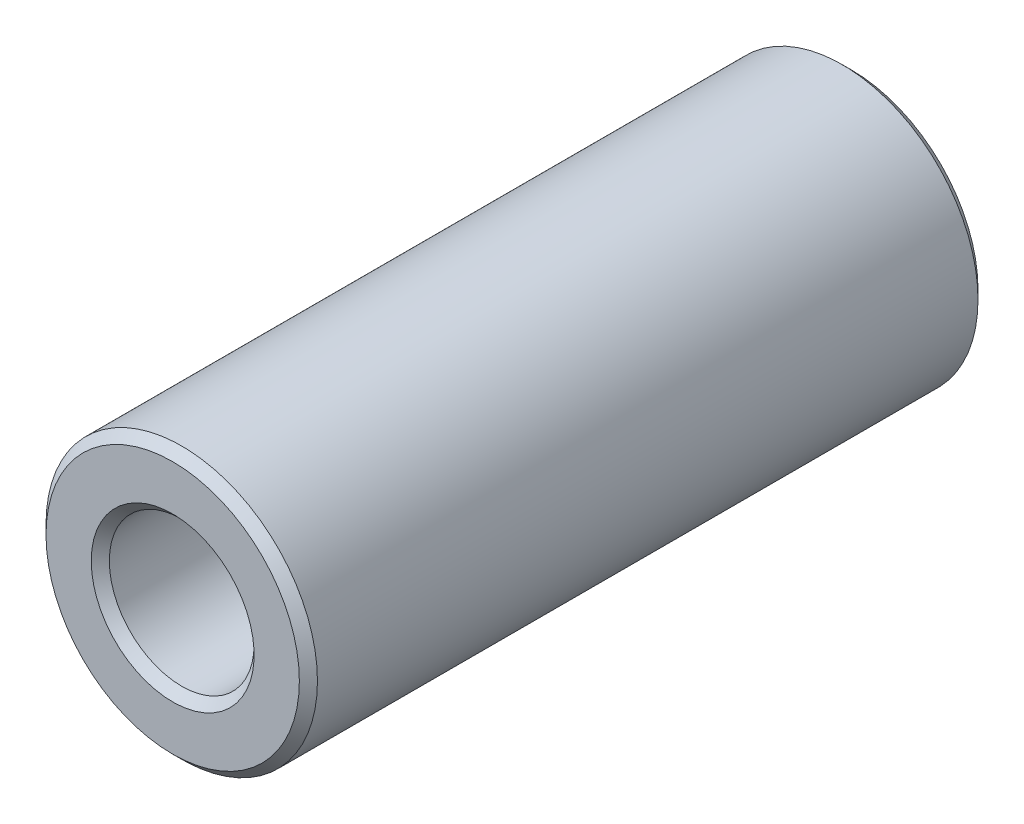
SolidWorks part; units mm, degrees
material "KS26"
ref_plane "正面" through (0, 0, 0) normal (0, 0, 1) x (1, 0, 0)
ref_plane "平面" through (0, 0, 0) normal (0, 1, 0) x (1, 0, 0)
ref_plane "右側面" through (0, 0, 0) normal (1, 0, 0) x (0, 0, -1)
sketch "ｽｹｯﾁ1" plane through (0, 0, 0) normal (1, 0, 0) x (0, 0, -1)
  line L0 (-7.1281, 0) -> (7.8719, 0) construction
  line L1 (0, 1.6) -> (0, 0) construction
  line L2 (-7.5, 3) -> (7.5, 3)
  line L3 (-7.5, 3) -> (-7.5, 1.6)
  line L4 (-7.5, 1.6) -> (7.5, 1.6)
  line L5 (7.5, 3) -> (7.5, 1.6)
  point P9 (7.5, 1.3218)
  dimension "D1" = 15
  dimension "D2" = 6
  dimension "D3" = 3.2
revolve "回転1" add sketch "ｽｹｯﾁ1" angle 360 about L0
chamfer "面取り1" distance 0.2 angle 45 4 edges at (1.6, 0, 7.5) (1.6, 0, -7.5) (3, 0, -7.5) (3, 0, 7.5)
